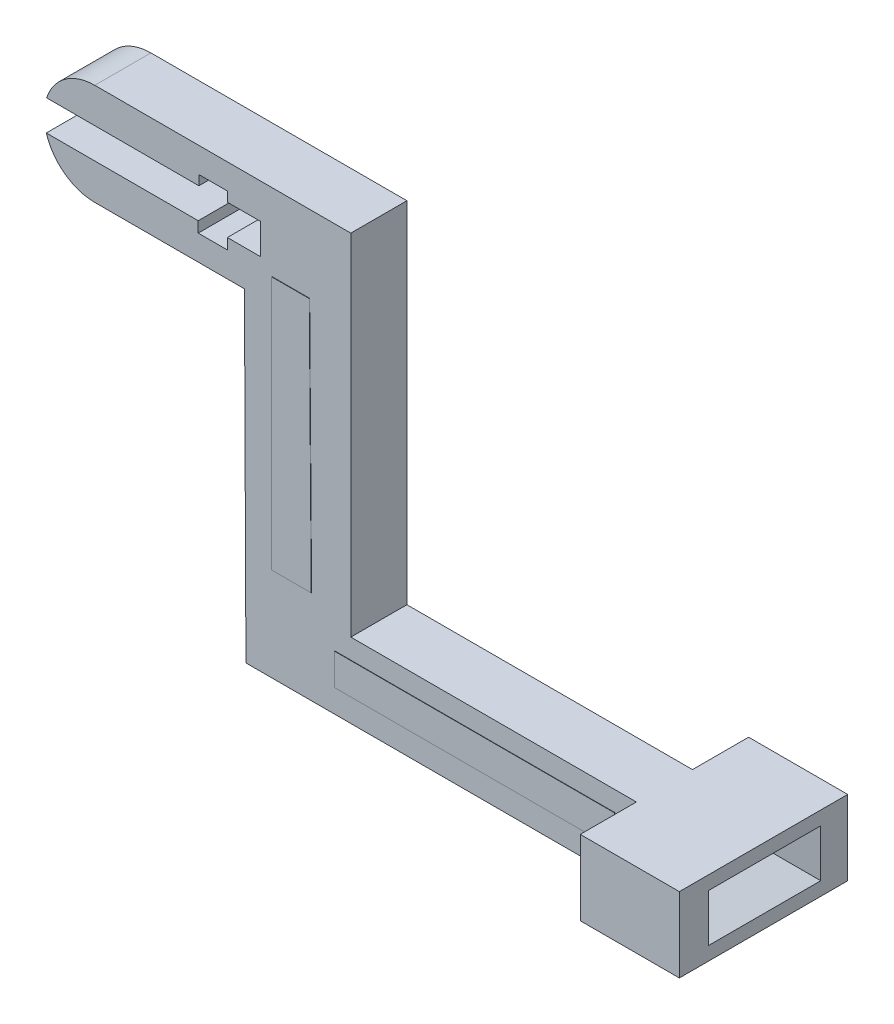
SolidWorks part; units mm, degrees
note: The reader was unsure of these and kept them because the rebuilt part matched: shared geometry of "Sketch2<6>", "Sketch2<10>".
ref_plane "Front Plane" through (0, 0, 0) normal (0, 0, 1) x (1, 0, 0)
ref_plane "Top Plane" through (0, 0, 0) normal (0, 1, 0) x (1, 0, 0)
ref_plane "Right Plane" through (0, 0, 0) normal (1, 0, 0) x (0, 0, -1)
sketch "Sketch2" plane through (0, 0, 0) normal (0, 0, 1) x (1, 0, 0)
  line L1 (0, 85.4575) -> (-40, 85.4575)
  line L3 (-40, 112.5741) -> (28.4296, 112.5741)
  line L15 (28.4296, 112.5741) -> (28.4296, 19.0493)
  line L17 (28.4296, 19.0493) -> (106.0073, 19.0493)
  line L18 (0.3979, -0.9507) -> (106.5613, -0.9507)
  line L19 (-52.8879, 103.2264) -> (10.9328, 103.2264)
  line L20 (18.032, 13.7176) -> (17.3744, 99.4895)
  line L21 (-52.9679, 95.0586) -> (7.3834, 95.0586)
  line L22 (7.3834, 95.0586) -> (7.3834, 17.7517)
  line L23 (18.032, 13.7176) -> (98.9934, 13.7176)
  line L24 (17.0155, 5.2969) -> (98.9934, 5.2969)
  line L25 (0, 85.4575) -> (0.3979, -0.9507)
  line L26 (-4.5653, 95.0586) -> (-4.5653, 92.1799)
  line L27 (-12.3569, 92.1799) -> (-4.5653, 92.1799)
  line L28 (-12.3569, 92.1799) -> (-12.3569, 95.0586)
  line L29 (-4.5653, 103.2264) -> (-4.5653, 105.8286)
  line L30 (-4.5653, 105.8286) -> (-12.1709, 105.8286)
  line L31 (-12.1709, 105.8286) -> (-12.1709, 103.2264)
  line L37 (4.2689, 103.2264) -> (4.2689, 95.0586)
  line L38 (7.3834, 91.9738) -> (17.432, 91.9738)
  line L39 (7.3834, 24.0957) -> (17.9524, 24.0957)
  line L40 (24.1979, 13.7176) -> (24.1979, 5.2969)
  line L45 (98.9934, 13.7176) -> (98.9934, 5.2969)
  line L47 (106.0073, 19.0493) -> (131.2003, 19.0493)
  line L48 (131.2003, 19.0493) -> (131.2003, -0.9507)
  line L49 (131.2003, -0.9507) -> (106.5613, -0.9507)
  line L50 (7.3834, 91.9738) -> (17.432, 91.9738)
  line L51 (17.9524, 24.0957) -> (7.3834, 24.0957)
  line L53 (7.3834, 91.9738) -> (7.3834, 24.0957)
  line L55 (17.9524, 24.0957) -> (17.432, 91.9738)
  arc A1 (-40, 112.5741) -> (-40, 85.4575) centre (-40, 99.0158) ccw
  arc A2 (10.9328, 103.2264) -> (17.3744, 99.4895) centre (10.9328, 95.8059) cw
  arc A3 (7.3834, 17.7517) -> (17.0155, 5.2969) centre (20.2519, 17.7517) ccw
  dimension "D1" = 40
  dimension "D2" = 20
extrude "Boss-Extrude1" add sketch "Sketch2" against normal blind 15
extrude "Cut-Extrude1" cut sketch "Sketch2<6>" against normal through all contours L30 L31 L19 L29 | L19 A1 L21 L37
sketch "Sketch2<6>" plane through (0, 0, 0) normal (0, 0, 1) x (1, 0, 0) same geometry as "Sketch2"
sketch "Sketch4" plane through (4.2689, 0, 0) normal (-1, 0, 0) x (0, 0, 1)
  line L1 (-14.304, 102.6869) -> (-0.715, 102.6869)
  line L2 (-14.304, 102.6869) -> (-14.304, 95.7546)
  line L3 (-14.304, 95.7546) -> (-0.715, 95.7546)
  line L4 (-0.715, 102.6869) -> (-0.715, 95.7546)
  line L5 (-14.304, 102.6869) -> (-0.715, 95.7546) construction
  line L6 (-14.304, 95.7546) -> (-0.715, 102.6869) construction
  point P0 (-7.5095, 99.2207)
extrude "Cut-Extrude2" cut sketch "Sketch4" against normal blind 11.112
extrude "Cut-Extrude3" cut sketch "Sketch2<10>" against normal blind 13.46 and the other way blind 0.1 contours L22 L39 L20 L38 | L45 L23 L40 L24
sketch "Sketch2<10>" plane through (0, 0, 0) normal (0, 0, 1) x (1, 0, 0) same geometry as "Sketch2"
sketch "Sketch6" plane through (0, 91.9738, 0) normal (0, -1, 0) x (-1, 0, 0)
  line L1 (-8.2134, 0.5283) -> (-17.0817, 0.5283)
  line L2 (-8.2134, 0.5283) -> (-8.2134, 12.7906)
  line L3 (-8.2134, 12.7906) -> (-17.0817, 12.7906)
  line L4 (-17.0817, 0.5283) -> (-17.0817, 12.7906)
  line L5 (-8.2134, 0.5283) -> (-17.0817, 12.7906) construction
  line L6 (-8.2134, 12.7906) -> (-17.0817, 0.5283) construction
  point P0 (-12.6475, 6.6595)
extrude "Cut-Extrude4" cut sketch "Sketch6" against normal blind 11.144 contours L2 L1 L4 L3
sketch "Sketch7" plane through (0, 24.0957, 0) normal (0, 1, 0) x (1, 0, 0)
  line L1 (17.2519, 0.5733) -> (8.0471, 0.5733)
  line L2 (17.2519, 0.5733) -> (17.2519, 12.8021)
  line L3 (17.2519, 12.8021) -> (8.0471, 12.8021)
  line L4 (8.0471, 0.5733) -> (8.0471, 12.8021)
  line L5 (17.2519, 0.5733) -> (8.0471, 12.8021) construction
  line L6 (17.2519, 12.8021) -> (8.0471, 0.5733) construction
  point P0 (12.6495, 6.6877)
extrude "Cut-Extrude5" cut sketch "Sketch7" against normal blind 13.904 contours L2 L1 L4 L3
sketch "Sketch8" plane through (24.1979, 0, 0) normal (1, 0, 0) x (0, 0, -1)
  line L1 (0.6284, 13.0128) -> (12.8283, 13.0128)
  line L2 (0.6284, 13.0128) -> (0.6284, 6.069)
  line L3 (0.6284, 6.069) -> (12.8283, 6.069)
  line L4 (12.8283, 13.0128) -> (12.8283, 6.069)
  line L5 (0.6284, 13.0128) -> (12.8283, 6.069) construction
  line L6 (0.6284, 6.069) -> (12.8283, 13.0128) construction
  point P0 (6.7283, 9.5409)
extrude "Cut-Extrude6" cut sketch "Sketch8" against normal blind 16.698
sketch "Sketch10" plane through (98.9934, 0, 0) normal (-1, 0, 0) x (0, 0, 1)
  line L5 (-13.0256, 13.2139) -> (-0.4113, 13.2139)
  line L6 (-13.0256, 13.2139) -> (-13.0256, 5.604)
  line L7 (-13.0256, 5.604) -> (-0.4113, 5.604)
  line L8 (-0.4113, 13.2139) -> (-0.4113, 5.604)
  line L9 (-13.0256, 13.2139) -> (-0.4113, 5.604) construction
  line L10 (-13.0256, 5.604) -> (-0.4113, 13.2139) construction
  point P0 (-6.7184, 9.4089)
sketch "Sketch12" plane through (0, 0, -15) normal (0, 0, -1) x (-1, 0, 0)
  line L0 (-131.2577, 19.0493) -> (-104.7651, 19.0493)
  line L5 (-131.2577, 19.0493) -> (-131.2577, -0.9507)
  line L6 (-131.2577, -0.9507) -> (-104.7651, -0.9507)
  line L7 (-104.7651, 19.0493) -> (-104.7651, -0.9507)
  line L8 (-28.4296, 19.0493) -> (-131.2003, 19.0493) construction
  line L9 (-0.3979, -0.9507) -> (-131.2003, -0.9507) construction
extrude "Boss-Extrude4" add sketch "Sketch12" along normal blind 15 and the other way blind 29.9999
sketch "Sketch13" plane through (131.2577, 0, 0) normal (1, 0, 0) x (0, 0, -1)
  line L1 (-7.2092, 15.3956) -> (22.7908, 15.3956)
  line L2 (-7.2092, 15.3956) -> (-7.2092, 2.6734)
  line L3 (-7.2092, 2.6734) -> (22.7908, 2.6734)
  line L4 (22.7908, 15.3956) -> (22.7908, 2.6734)
  line L5 (-7.2092, 15.3956) -> (22.7908, 2.6734) construction
  line L6 (-7.2092, 2.6734) -> (22.7908, 15.3956) construction
  point P0 (7.7908, 9.0345)
extrude "Cut-Extrude9" cut sketch "Sketch13" against normal blind 15 draft 24 contours L2 L1 L4 L3
extrude "Cut-Extrude15" cut sketch "Sketch10" against normal blind 20.842 draft 11
sketch "Sketch14" plane through (0, 0, 0) normal (0, 0, 1) x (1, 0, 0)
  line L0 (101.1092, 13.5872) -> (101.1092, 5.1927)
  line L1 (101.1092, 13.6252) -> (101.1092, 5.1927) construction
  line L2 (101.1092, 5.1927) -> (104.7651, 4.4821)
  line L4 (104.7651, 14.3358) -> (101.1092, 13.5872)
  line L5 (104.7651, 14.3358) -> (101.1092, 13.6252) construction
  line L9 (104.7651, 14.3358) -> (104.7651, 4.4821)
extrude "Boss-Extrude7" add sketch "Sketch14" along normal blind 0.7 separate body
sketch "Sketch15" plane through (0, 0, 0) normal (0, 0, 1) x (1, 0, 0)
  line L0 (7.3834, 91.9738) -> (17.432, 91.9738)
  line L1 (17.432, 91.9738) -> (17.9524, 24.0957)
  line L2 (7.3834, 24.0957) -> (17.9524, 24.0957)
  line L3 (7.3834, 24.0957) -> (7.3834, 91.9738)
  line L4 (24.1979, 13.7176) -> (24.1979, 5.2969)
  line L5 (24.1979, 5.2969) -> (98.9934, 5.2969)
  line L6 (98.9934, 5.2969) -> (98.9934, 13.7176)
extrude "Boss-Extrude10" add sketch "Sketch15" along normal blind 0.1 separate body
